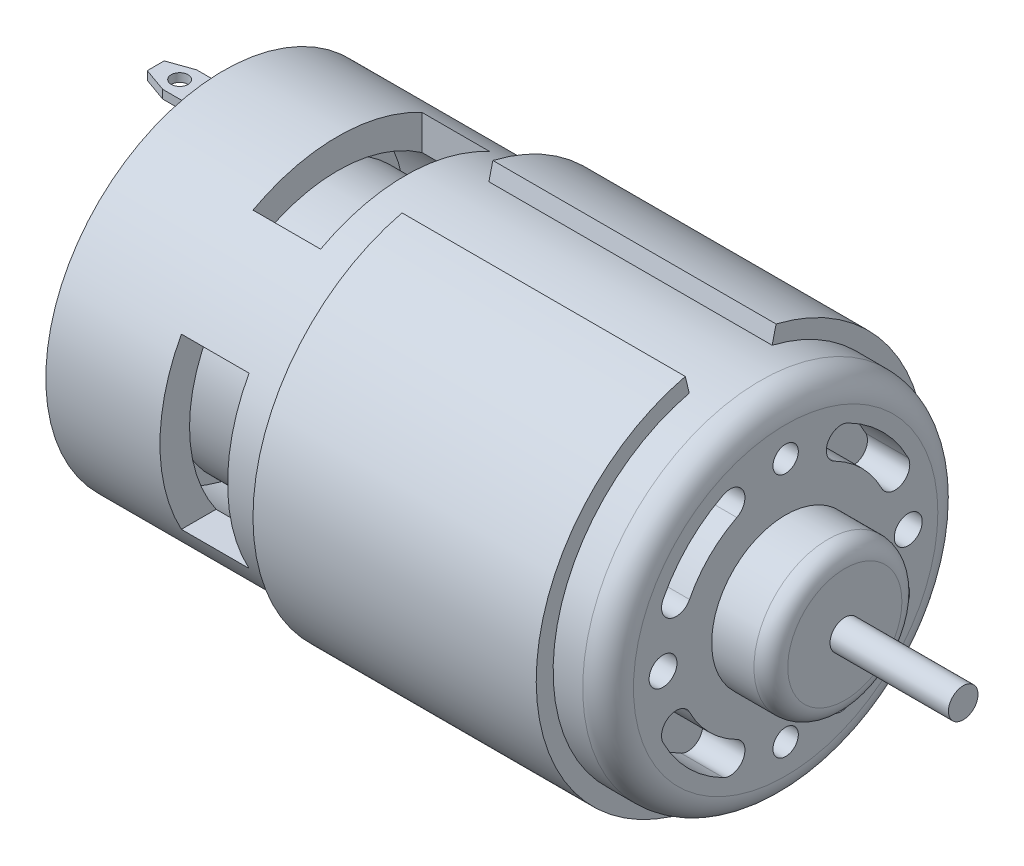
SolidWorks part; units mm, degrees
note: The reader was unsure of these and kept them because the rebuilt part matched: shared geometry of "Sketch5<3>".
material "1060 Alloy"
ref_plane "Front Plane" through (0, 0, 0) normal (0, 0, 1) x (1, 0, 0)
ref_plane "Top Plane" through (0, 0, 0) normal (0, 1, 0) x (1, 0, 0)
ref_plane "Right Plane" through (0, 0, 0) normal (1, 0, 0) x (0, 0, -1)
sketch "Sketch1" plane through (0, 0, 0) normal (1, 0, 0) x (0, 0, -1)
  circle A0 centre (0, 0) radius 21
  dimension "D1" = 42
extrude "Boss-Extrude1" add sketch "Sketch1" along normal blind 66.5
fillet "Fillet1" radius 3 1 edges at (66.5, 0, -21)
sketch "Sketch2" plane through (66.5, 0, 0) normal (1, 0, 0) x (0, 0, -1)
  circle A0 centre (0, 0) radius 8.75
  dimension "D1" = 17.5
extrude "Boss-Extrude2" add sketch "Sketch2" along normal blind 7
fillet "Fillet2" radius 2 1 edges at (73.5, 0, -8.75)
sketch "Sketch3" plane through (73.5, 0, 0) normal (1, 0, 0) x (0, 0, -1)
  circle A0 centre (0, 0) radius 1.75
  dimension "D1" = 3.5
extrude "Boss-Extrude3" add sketch "Sketch3" along normal blind 14
ref_plane "Plane1" through (60, 0, 0) normal (1, 0, 0) x (0, 0, -1)
sketch "Sketch4" plane through (60, 0, 0) normal (1, 0, 0) x (0, 0, -1)
  line L0 (-5.3694, 22.3645) -> (-4.9025, 20.4197)
  line L1 (4.9025, 20.4197) -> (5.4896, 22.8652)
  circle A0 centre (0, 0) radius 23
  circle A1 centre (0, 0) radius 21 construction
  circle A2 centre (0, 0) radius 21
  dimension "D1" = 46
  dimension "D2" = 42
extrude "Boss-Extrude4" add sketch "Sketch4" against normal blind 33.5 contours A2 L0 A0 L1
sketch "Sketch5" plane through (0, 0, 0) normal (-1, 0, 0) x (0, 0, 1)
  line L0 (0, 21) -> (0, -21) construction
  line L2 (-2, 17.5) -> (2, 17.5)
  line L3 (-2, 17.5) -> (-2, 16.5)
  line L4 (-2, 16.5) -> (2, 16.5)
  line L5 (2, 17.5) -> (2, 16.5)
  line L6 (-2, 17.5) -> (2, 16.5) construction
  line L7 (-2, 16.5) -> (2, 17.5) construction
  line L8 (-2, -16.5) -> (2, -16.5)
  line L9 (-2, -16.5) -> (-2, -17.5)
  line L10 (-2, -17.5) -> (2, -17.5)
  line L11 (2, -16.5) -> (2, -17.5)
  line L12 (-2, -16.5) -> (2, -17.5) construction
  line L13 (-2, -17.5) -> (2, -16.5) construction
  circle A0 centre (0, 0) radius 21 construction
  arc A1 (-4.9025, 20.4197) -> (4.9025, 20.4197) centre (0, 0) ccw construction
  circle A2 centre (0, 0) radius 19
  point P7 (0, 17)
  point P12 (0, -17)
  dimension "D5" = 2
  dimension "D1" = 34
  dimension "D2" = 17
  dimension "D3" = 4
  dimension "D4" = 1
extrude "Cut-Extrude1" cut sketch "Sketch5" against normal blind 2
extrude "Boss-Extrude5" add sketch "Sketch5<3>" along normal blind 8 contours L4 L5 L2 L3 | L8 L11 L10 L9
sketch "Sketch5<3>" plane through (0, 0, 0) normal (-1, 0, 0) x (0, 0, 1) same geometry as "Sketch5"
sketch "Sketch6" plane through (0, -17.5, 0) normal (0, -1, 0) x (1, 0, 0)
  line L0 (-5.1716, -2) -> (-8, -1)
  line L1 (2, -2) -> (-8, -2) construction
  line L2 (-8, -2) -> (-8, 2) construction
  line L3 (-8, -1) -> (-8, 1)
  line L4 (-8, 1) -> (-5.1716, 2)
  line L5 (2, 2) -> (-8, 2) construction
  line L6 (-5.1716, -2) -> (-8, -2)
  line L7 (-8, -2) -> (-8, -1)
  line L8 (-7.7692, 1.1937) -> (-8, 1)
  line L9 (-8, 1) -> (-8, 2)
  line L10 (-8, 2) -> (-5.1716, 2)
  dimension "D1" = 3
  dimension "D2" = 1
extrude "Cut-Extrude2" cut sketch "Sketch6" against normal blind 37
ref_plane "Plane2" through (0, 21, 0) normal (0, 1, 0) x (1, 0, 0)
sketch "Sketch7" plane through (0, 21, 0) normal (0, 1, 0) x (1, 0, 0)
  line L0 (0, 0) -> (29.2331, 0) construction
  line L1 (21.5, -21) -> (21.5, 21) construction
  line L2 (0, -21) -> (26.5, -21) construction
  line L3 (26.5, 21) -> (0, 21) construction
  line L4 (26.5, 23) -> (26.5, -23) construction
  line L6 (21.5, -10) -> (13.5, -10)
  line L7 (21.5, -10) -> (21.5, 10)
  line L8 (21.5, 10) -> (13.5, 10)
  line L9 (13.5, -10) -> (13.5, 10)
  dimension "D1" = 5
  dimension "D2" = 10
  dimension "D3" = 10
  dimension "D4" = 8
extrude "Cut-Extrude3" cut sketch "Sketch7" against normal through all
pattern_circular "CirPattern1" count 2 every 90 about axis through (0, 0, 0) along (-1, 0, 0) of "Cut-Extrude3"
sketch "Sketch9" plane through (2, 0, 0) normal (-1, 0, 0) x (0, 0, 1)
  circle A0 centre (0, 0) radius 17.5
  dimension "D1" = 35
extrude "Boss-Extrude6" add sketch "Sketch9" against normal up to surface (64.5 mm away) up to face at (66.5, 0, -8.75)
sketch "Sketch10" plane through (0, 17.5, 0) normal (0, 1, 0) x (1, 0, 0)
  line L0 (-8, 0) -> (0, 0) construction
  line L1 (-8, 1) -> (-8, -1) construction
  line L2 (-5.1716, 2) -> (-5.1716, -2) construction
  line L3 (-8, 1) -> (-5.1716, 2) construction
  line L4 (2, 2) -> (-5.1716, 2) construction
  circle A0 centre (-5.1716, 0) radius 1
  dimension "D1" = 2
extrude "Cut-Extrude4" cut sketch "Sketch10" against normal through all and the other way through all
sketch "Sketch11" plane through (66.5, 0, 0) normal (1, 0, 0) x (0, 0, -1)
  line L0 (18, 0) -> (-18, 0) construction
  line L1 (0, 14.5) -> (0, -14.5) construction
  line L2 (-6.5648, 12.9288) -> (0, 14.5)
  line L3 (-12.9288, 6.5648) -> (-14.5, 0)
  circle A0 centre (0, 0) radius 14.5
  circle A1 centre (0, 0) radius 18 construction
  circle A2 centre (0, -14.5) radius 1.5
  circle A3 centre (0, 14.5) radius 1.5
  arc A4 (-12.9288, 6.5648) -> (-6.5648, 12.9288) centre (0, 0) cw construction
  arc A5 (-7.3571, 14.4891) -> (-14.4891, 7.3571) centre (0, 0) ccw
  arc A6 (-5.7725, 11.3684) -> (-11.3684, 5.7725) centre (0, 0) ccw
  arc A7 (-5.7725, 11.3684) -> (-7.3571, 14.4891) centre (-6.5648, 12.9288) ccw
  arc A8 (-14.4891, 7.3571) -> (-11.3684, 5.7725) centre (-12.9288, 6.5648) ccw
  arc A9 (6.5648, 12.9288) -> (12.9288, 6.5648) centre (0, 0) cw construction
  arc A10 (14.4891, 7.3571) -> (7.3571, 14.4891) centre (0, 0) ccw
  arc A11 (11.3684, 5.7725) -> (5.7725, 11.3684) centre (0, 0) ccw
  arc A12 (11.3684, 5.7725) -> (14.4891, 7.3571) centre (12.9288, 6.5648) ccw
  arc A13 (7.3571, 14.4891) -> (5.7725, 11.3684) centre (6.5648, 12.9288) ccw
  arc A14 (12.9288, -6.5648) -> (6.5648, -12.9288) centre (0, 0) cw construction
  arc A15 (7.3571, -14.4891) -> (14.4891, -7.3571) centre (0, 0) ccw
  arc A16 (5.7725, -11.3684) -> (11.3684, -5.7725) centre (0, 0) ccw
  arc A17 (5.7725, -11.3684) -> (7.3571, -14.4891) centre (6.5648, -12.9288) ccw
  arc A18 (14.4891, -7.3571) -> (11.3684, -5.7725) centre (12.9288, -6.5648) ccw
  arc A19 (-6.5648, -12.9288) -> (-12.9288, -6.5648) centre (0, 0) cw construction
  arc A20 (-14.4891, -7.3571) -> (-7.3571, -14.4891) centre (0, 0) ccw
  arc A21 (-11.3684, -5.7725) -> (-5.7725, -11.3684) centre (0, 0) ccw
  arc A22 (-11.3684, -5.7725) -> (-14.4891, -7.3571) centre (-12.9288, -6.5648) ccw
  arc A23 (-7.3571, -14.4891) -> (-5.7725, -11.3684) centre (-6.5648, -12.9288) ccw
  point P15 (-10.253, 10.253)
  point P28 (10.253, 10.253)
  point P35 (10.253, -10.253)
  point P42 (-10.253, -10.253)
  dimension "D1" = 29
  dimension "D2" = 3
  dimension "D3" = 3
  dimension "D4" = 3.5
  dimension "D5" = 9
  dimension "D6" = 4
hole_wizard "M4 Tapped Hole1" positions "3DSketch1" profile "Sketch12" tap size "M4" standard "KS"
sketch3d "3DSketch1"
  line L0 (66.5, 0, -18) -> (66.5, 0, 18) construction
  circle A0 centre (66.5, 0, 0) radius 14.5 construction
  point P0 (66.5, 0, 14.5)
  point P4 (81, 0, 0)
  point P7 (66.5, 0, -14.5)
cosmetic thread "Hole Thread1" parameters "D1"=8, "D2"=4
cosmetic thread "Hole Thread2" parameters "D1"=8, "D2"=4
sketch "Sketch12" plane through (66.5, 0, 14.5) normal (0, 1, 0) x (0, 0, -1)
  line L0 (0, 0) -> (0, 11.0914)
  line L1 (0, 11.0914) -> (1.65, 10.1)
  line L2 (1.65, 10.1) -> (1.65, 0)
  line L5 (1.65, 0) -> (0, 0)
  line L10 (0, 11.0914) -> (-1.65, 10.1) construction
  line L11 (0, -6.35) -> (0, 107.95) construction
  dimension "Tap Drill Dia." = 3.3
  dimension "Tap Drill Depth" = 10.1
  dimension "Drill Angle" = 118
extrude "Cut-Extrude6" cut sketch "Sketch11" against normal blind 5 contours L3 A8 A6 A7 L2 A0 | A20 A23 A0 A22 | A0 A23 A21 A22 | A0 A2 | A0 A2 | A0 A18 A16 A17 | A15 A18 A0 A17 | A0 A13 A11 A12 | A10 A13 A0 A12 | L2 A3 A0 | A0 A3 L2 | A0 A3 | L2 A7 A0 | A0 A8 L3
sketch "Sketch13" plane through (2, 0, 0) normal (-1, 0, 0) x (0, 0, 1)
  circle A0 centre (0, 0) radius 15
  dimension "D1" = 30
extrude "Boss-Extrude7" add sketch "Sketch13" along normal blind 1
chamfer "Chamfer1" distance 2 distance2 3.5 1 edges at (1, 0, 15) first distance on face at (1, 0, 15)
sketch "Sketch15" plane through (2, 0, 0) normal (-1, 0, 0) x (0, 0, 1)
  line L0 (1, 17) -> (-1, 17) construction
  line L1 (1, 17.5) -> (1, 16.5) construction
  line L2 (-1, 17.5) -> (-1, 16.5) construction
  line L3 (0, 17.5) -> (0, 16.5315) construction
  line L4 (19, 0) -> (-19, 0) construction
  line L5 (3, 19.5) -> (-3, 19.5)
  line L6 (3, 19.5) -> (3, 14.5)
  line L7 (3, 14.5) -> (-3, 14.5)
  line L8 (-3, 19.5) -> (-3, 14.5)
  line L9 (3, 19.5) -> (-3, 14.5) construction
  line L10 (3, 14.5) -> (-3, 19.5) construction
  line L11 (-3, -19.5) -> (-3, -14.5)
  line L12 (3, -19.5) -> (-3, -19.5)
  line L13 (3, -19.5) -> (3, -14.5)
  line L14 (3, -14.5) -> (-3, -14.5)
  circle A0 centre (0, 0) radius 19 construction
  circle A1 centre (0, 0) radius 19 construction
  point P10 (0, 17)
  dimension "D1" = 6
  dimension "D2" = 5
extrude "Boss-Extrude8" add sketch "Sketch15" along normal blind 1
sketch "Sketch16" plane through (2, 0, 0) normal (-1, 0, 0) x (0, 0, 1)
  line L0 (-19, 0) -> (19, 0) construction
  arc A0 (-3, 18.7617) -> (-3, -18.7617) centre (0, 0) ccw construction
chamfer "Chamfer2" distance 1 angle 32 6 edges at (1, -16.6308, -3) (1, -14.5, 0) (1, -16.6308, 3) (1, 16.6308, 3) (1, 16.6308, -3) (1, 14.5, 0) first distance on face at (1, -17, 0) first distance on face at (1, 17, 0)
sketch "Sketch17" plane through (1, 0, 0) normal (-1, 0, 0) x (0, 0, 1)
  line L0 (-19, 0) -> (19, 0) construction
  circle A0 centre (0, 0) radius 6.1849
extrude "Boss-Extrude9" add sketch "Sketch17" along normal blind 3
fillet "Fillet3" radius 1 1 edges at (-2, 0, 6.1849)
sketch "Sketch19" plane through (-2, 0, 0) normal (-1, 0, 0) x (0, 0, 1)
  circle A0 centre (0, 0) radius 2
  dimension "D1" = 4
extrude "Boss-Extrude10" add sketch "Sketch19" along normal blind 3
fillet "Fillet4" radius 1 1 edges at (-5, 0, 2)
sketch "Sketch20" plane through (1, 0, 0) normal (-1, 0, 0) x (0, 0, 1)
  line L0 (-9, 0) -> (9, 0) construction
  line L1 (0, 0) -> (6.364, -6.364) construction
  line L2 (0, 11.5) -> (0, -11.5) construction
  line L3 (0, 0) -> (-6.364, 6.364) construction
  circle A0 centre (0, 0) radius 9
  circle A1 centre (0, 0) radius 11.5 construction
  arc A2 (4.1002, 8.0118) -> (8.0118, 4.1002) centre (0, 0) cw construction
  arc A3 (-8.0118, 4.1002) -> (-4.1002, 8.0118) centre (0, 0) cw construction
  arc A4 (-4.6696, 9.1245) -> (-9.1245, 4.6696) centre (0, 0) ccw
  arc A5 (-3.5307, 6.899) -> (-6.899, 3.5307) centre (0, 0) ccw
  arc A6 (-3.5307, 6.899) -> (-4.6696, 9.1245) centre (-4.1002, 8.0118) ccw
  arc A7 (-9.1245, 4.6696) -> (-6.899, 3.5307) centre (-8.0118, 4.1002) ccw
  arc A8 (9.1245, 4.6696) -> (4.6696, 9.1245) centre (0, 0) ccw
  arc A9 (6.899, 3.5307) -> (3.5307, 6.899) centre (0, 0) ccw
  arc A10 (6.899, 3.5307) -> (9.1245, 4.6696) centre (8.0118, 4.1002) ccw
  arc A11 (4.6696, 9.1245) -> (3.5307, 6.899) centre (4.1002, 8.0118) ccw
  arc A12 (8.0118, -4.1002) -> (4.1002, -8.0118) centre (0, 0) cw construction
  arc A13 (4.6696, -9.1245) -> (9.1245, -4.6696) centre (0, 0) ccw
  arc A14 (3.5307, -6.899) -> (6.899, -3.5307) centre (0, 0) ccw
  arc A15 (3.5307, -6.899) -> (4.6696, -9.1245) centre (4.1002, -8.0118) ccw
  arc A16 (9.1245, -4.6696) -> (6.899, -3.5307) centre (8.0118, -4.1002) ccw
  arc A17 (-4.1002, -8.0118) -> (-8.0118, -4.1002) centre (0, 0) cw construction
  arc A18 (-9.1245, -4.6696) -> (-4.6696, -9.1245) centre (0, 0) ccw
  arc A19 (-6.899, -3.5307) -> (-3.5307, -6.899) centre (0, 0) ccw
  arc A20 (-6.899, -3.5307) -> (-9.1245, -4.6696) centre (-8.0118, -4.1002) ccw
  arc A21 (-4.6696, -9.1245) -> (-3.5307, -6.899) centre (-4.1002, -8.0118) ccw
  point P8 (-6.364, 6.364)
  point P24 (6.364, 6.364)
  point P32 (6.364, -6.364)
  point P39 (-6.364, -6.364)
  dimension "D1" = 2.5
  dimension "D2" = 2.5
  dimension "D3" = 2.8
  dimension "D4" = 45
  dimension "D5" = 4
extrude "Cut-Extrude7" cut sketch "Sketch20" against normal blind 5 contours A0 A21 A19 A20 | A18 A21 A0 A20 | A0 A7 A5 A6 | A4 A7 A0 A6 | A0 A11 A9 A10 | A8 A11 A0 A10 | A0 A16 A14 A15 | A13 A16 A0 A15
ref_plane "Plane4" through (30, 0, 0) normal (1, 0, 0) x (0, 0, -1)
sketch "Sketch22" plane through (30, 0, 0) normal (1, 0, 0) x (0, 0, -1)
  circle A0 centre (0, 0) radius 15
  circle A1 centre (0, 0) radius 17.5
  dimension "D1" = 35
  dimension "D2" = 30
extrude "Cut-Extrude8" cut sketch "Sketch22" against normal blind 26
ref_plane "Plane5" through (4, 0, 0) normal (1, 0, 0) x (0, 0, -1)
sketch "Sketch23" plane through (4, 0, 0) normal (1, 0, 0) x (0, 0, -1)
  circle A0 centre (0, 0) radius 17.5
  circle A1 centre (0, 0) radius 6
  dimension "D1" = 35
  dimension "D2" = 12
extrude "Cut-Extrude9" cut sketch "Sketch23" along normal blind 5
